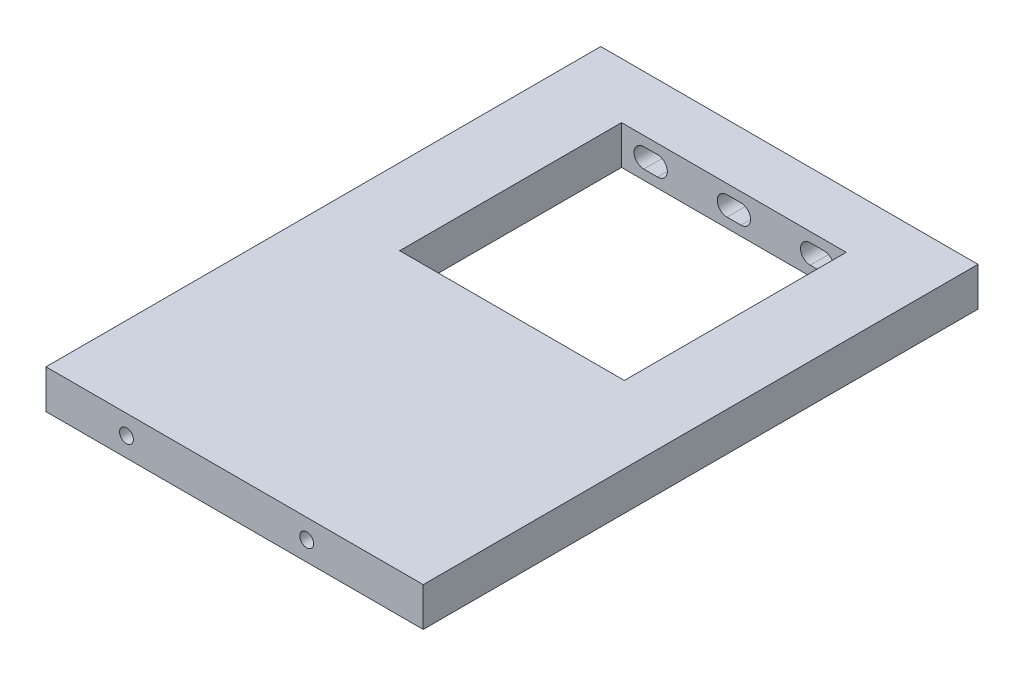
SolidWorks part; units mm, degrees
other "Markup1"
sketch "Sketch11" plane through (-148, 207, 138) normal (-0.4174, 0.5856, 0.6948) x (0.7295, -0.24, 0.6405)
ref_plane "Front Plane" through (0, 0, 0) normal (0, 0, 1) x (1, 0, 0)
ref_plane "Top Plane" through (0, 0, 0) normal (0, 1, 0) x (1, 0, 0)
ref_plane "Right Plane" through (0, 0, 0) normal (1, 0, 0) x (0, 0, -1)
sketch "Sketch1" plane through (0, 0, 0) normal (0, 0, 1) x (1, 0, 0)
  line L1 (-148, 235) -> (-148, 170) construction
  line L4 (-148, 207) -> (-21, 207)
  line L8 (-148, 197.5) -> (-148, 193)
  line L10 (-148, 197.5) -> (-148, 207)
  line L11 (-148, 193) -> (-24, 193)
  line L13 (-148, 207) -> (-21, 207)
  line L16 (-21, 207) -> (-12, 207)
  line L17 (-12, 207) -> (-12, 193)
  line L18 (-12, 193) -> (-24, 193)
extrude "Boss-Extrude1" add sketch "Sketch1" along normal up to surface (200 mm away) contours L4 L10 L8 L11 region at (-80, 200, 0)
sketch "Sketch3" plane through (0, 207, 0) normal (0, 1, 0) x (1, 0, 0)
  line L4 (-32, -180) -> (-32, -20)
  line L6 (-32, -20) -> (-128, -20)
  line L7 (-42, -20) -> (-118, -20)
  line L8 (-118, -100) -> (-42, -100)
  line L11 (-42, -20) -> (-39.5, -20)
  line L12 (-128, -20) -> (-128, -180)
  line L15 (-39.5, -20) -> (-39.5, -100)
  line L16 (-39.5, -100) -> (-42, -100)
  line L17 (-118, -20) -> (-120.5, -20)
  line L22 (-120.5, -20) -> (-120.5, -100)
  line L23 (-128, -180) -> (-32, -180)
  line L24 (-120.5, -100) -> (-118, -100)
  dimension "D1" = 20
extrude "Cut-Extrude1" cut sketch "Sketch3" against normal through all contours L7 region at (-80, 207, 60)
sketch "Sketch5" plane through (0, 0, 20) normal (0, 0, 1) x (1, 0, 0)
  circle A3 centre (-110, 200) radius 3
  circle A4 centre (-80, 200) radius 3
  circle A5 centre (-50, 200) radius 3
hole_wizard "Ø6.0mm Dowel Slot1" positions "Sketch6" profile "Sketch7" size "Ø6.0" standard "ANSI Metric" slot yes end condition through all
sketch "Sketch6" plane through (0, 0, 20) normal (0, 0, 1) x (1, 0, 0)
  line L0 (-116, 200) -> (-104, 200) construction
  point P12 (-110, 200)
  point P15 (-80, 200)
  point P18 (-50, 200)
  dimension "D1" = 12
sketch "Sketch7" plane through (-110, 200, 20) normal (1, 0, 0) x (0, -1, 0)
  line L0 (0, 0) -> (0, 20)
  line L1 (0, 20) -> (3.5, 20)
  line L2 (3.5, 20) -> (3.5, 0)
  line L5 (3.5, 0) -> (0, 0)
  line L11 (0, -6.35) -> (0, 107.95) construction
  dimension "Thru Hole Dia." = 7
  dimension "Thru Hole Depth" = 20
sketch "Sketch8" plane through (0, 0, 200) normal (0, 0, 1) x (1, 0, 0)
  line L0 (-48, 200) -> (-54, 200)
  line L2 (-148, 200) -> (-119, 200)
hole_wizard "M6x1.0 Tapped Hole1" positions "Sketch9" profile "Sketch10" tap size "M6x1.0" standard "ANSI Metric"
sketch "Sketch9" plane through (0, 0, 200) normal (0, 0, 1) x (1, 0, 0)
  point P0 (-119, 200)
  point P3 (-54, 200)
sketch "Sketch10" plane through (-119, 200, 200) normal (1, 0, 0) x (0, -1, 0)
  line L0 (0, 0) -> (0, 23)
  line L1 (0, 23) -> (2.5, 21.4978)
  line L2 (2.5, 21.4978) -> (2.5, 0)
  line L5 (2.5, 0) -> (0, 0)
  line L10 (0, 23) -> (-2.5, 21.4978) construction
  line L11 (0, -6.35) -> (0, 107.95) construction
  dimension "Tap Drill Dia." = 5
  dimension "Tap Drill Depth" = 23
  dimension "Drill Angle" = 118
cosmetic thread "Hole Thread1" parameters "D1"=20, "D2"=6
cosmetic thread "Hole Thread2" parameters "D1"=20, "D2"=6
